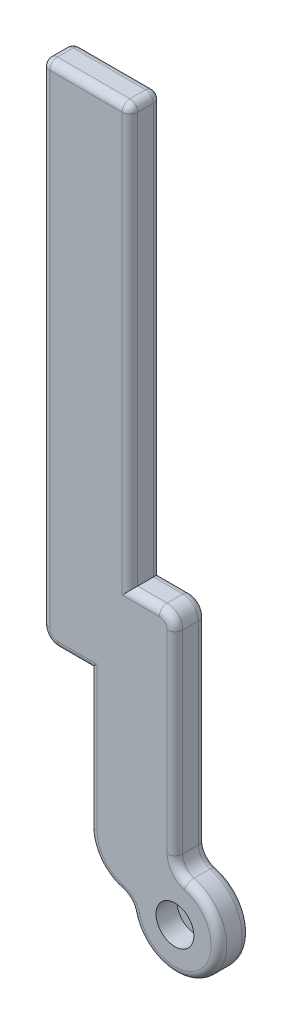
SolidWorks part; units mm, degrees
ref_plane "Plan de face" through (0, 0, 0) normal (0, 0, 1) x (1, 0, 0)
ref_plane "Plan de dessus" through (0, 0, 0) normal (0, 1, 0) x (1, 0, 0)
ref_plane "Plan de droite" through (0, 0, 0) normal (1, 0, 0) x (0, 0, -1)
sketch "Esquisse3" plane through (0, 0, 0) normal (0, 0, 1) x (1, 0, 0)
  line L0 (0, 0) -> (0, 65)
  line L2 (11.3, 65) -> (11.3, 11.3)
  line L3 (11.3, 11.3) -> (22.73, 11.3)
  line L4 (22.73, 11.3) -> (22.73, -23)
  line L6 (11.43, -23) -> (11.43, 0)
  line L7 (11.43, 0) -> (0, 0)
  line L8 (0, 65) -> (11.3, 65)
  line L9 (11.3, 0) -> (11.43, 0) construction
  arc A1 (11.43, -23) -> (22.73, -23) centre (17.08, -23) ccw
  dimension "D1" = 5.65
  dimension "D2" = 17.08
  dimension "D6" = 11.3
  dimension "D3" = 11.3
  dimension "D4" = 23
  dimension "D5" = 65
extrude "Boss.-Extru.1" add sketch "Esquisse3" along normal blind 4
sketch "Esquisse4" plane through (0, 0, 4) normal (0, 0, 1) x (1, 0, 0)
  circle A0 centre (17.08, -23) radius 2.43
  dimension "D1" = 4.86
extrude "Enlèv. mat.-Extru.1" cut sketch "Esquisse4" against normal blind 2.7
sketch "Esquisse5" plane through (0, 0, 1.3) normal (0, 0, 1) x (1, 0, 0)
  circle A0 centre (17.08, -23) radius 0.75
  dimension "D1" = 1.5
extrude "Enlèv. mat.-Extru.2" cut sketch "Esquisse5" against normal up to vertex (1.3 mm away) up to point (22.73, -23, 0)
fillet "Congé1" radius 1 2 edges at (0, 65, 2) (11.3, 65, 2)
sketch "Esquisse6" plane through (0, 0, 4) normal (0, 0, 1) x (1, 0, 0)
  line L0 (11.43, -23) -> (6.08, -23)
  line L1 (6.08, -23) -> (6.08, 0)
  line L2 (0, 0) -> (11.43, 0) construction
  line L3 (6.08, 0) -> (11.43, 0)
  line L4 (11.43, 0) -> (11.43, -23)
  circle A0 centre (17.08, -23) radius 0.75 construction
  dimension "D1" = 11
extrude "Boss.-Extru.2" add sketch "Esquisse6" against normal up to vertex (4 mm away) up to point (11.43, 0, 0)
fillet "Congé4" radius 5.45 1 edges at (6.08, -23, 2)
sketch "Esquisse7" plane through (0, 0, 4) normal (0, 0, 1) x (1, 0, 0)
  line L0 (17.08, -17.35) -> (17.08, 11.3)
  line L1 (22.73, 11.3) -> (11.3, 11.3) construction
  line L2 (17.08, 11.3) -> (22.73, 11.3)
  line L3 (22.73, 11.3) -> (22.73, -23)
  arc A0 (22.73, -23) -> (17.08, -17.35) centre (17.08, -23) ccw
extrude "Enlèv. mat.-Extru.3" cut sketch "Esquisse7" against normal up to vertex (4 mm away) up to point (22.73, 11.3, 0)
fillet "Congé5" radius 2 2 edges at (17.08, 11.3, 2) (0, 0, 2)
fillet "Congé6" radius 2 2 edges at (11.43, -23, 2) (17.08, -17.35, 2)
fillet "Congé7" radius 1 30 edges at (11.0665, -23.3598, 4) (21.0088, -27.0604, 4) (17.4916, -16.8314, 4) (7.2137, -20.8784, 4) (17.08, -3.158, 4) (6.08, -8.7755, 4) (4.04, 0, 4) (0.5858, 0.5858, 4) (16.4942, 10.7142, 4) (13.19, 11.3, 4) (0, 33, 4) (11.3, 37.65, 4) (11.0071, 64.7071, 4) (0.2929, 64.7071, 4) (5.65, 65, 4) (0.2929, 64.7071, 0) (5.65, 65, 0) (11.0071, 64.7071, 0) (0, 33, 0) (11.3, 37.65, 0) (13.19, 11.3, 0) (16.4942, 10.7142, 0) (0.5858, 0.5858, 0) (4.04, 0, 0) (6.08, -8.7755, 0) (7.2137, -20.8784, 0) (17.08, -3.158, 0) (11.0665, -23.3598, 0) (17.4916, -16.8314, 0) (21.0088, -27.0604, 0)
